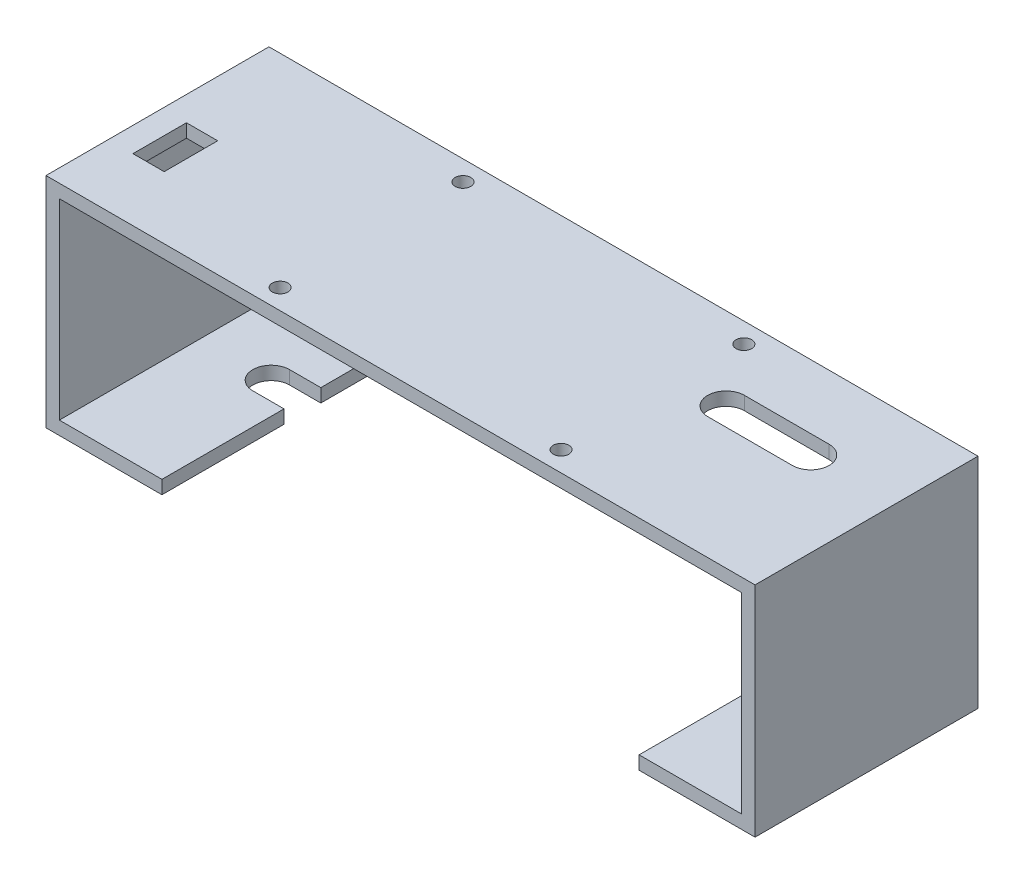
SolidWorks part; units mm, degrees
ref_plane "Front" through (0, 0, 0) normal (0, 0, 1) x (1, 0, 0)
ref_plane "Top" through (0, 0, 0) normal (0, 1, 0) x (1, 0, 0)
ref_plane "Right" through (0, 0, 0) normal (1, 0, 0) x (0, 0, -1)
sketch "Sketch1" plane through (0, 0, 0) normal (0, 1, 0) x (1, 0, 0)
  line L1 (-31.5, 20.5) -> (31.5, 20.5) construction
  line L2 (-31.5, 20.5) -> (-31.5, -20.5) construction
  line L3 (-31.5, -20.5) -> (31.5, -20.5) construction
  line L4 (31.5, 20.5) -> (31.5, -20.5) construction
  line L5 (-31.5, 20.5) -> (31.5, -20.5) construction
  line L6 (-31.5, -20.5) -> (31.5, 20.5) construction
  line L7 (-38.5, -18.5) -> (-24.5, -18.5) construction
  line L8 (-38.5, -18.5) -> (-38.5, 18.5) construction
  line L9 (-38.5, 18.5) -> (-24.5, 18.5) construction
  line L10 (-24.5, -18.5) -> (-24.5, 18.5) construction
  line L11 (-38.5, -18.5) -> (-24.5, 18.5) construction
  line L12 (-38.5, 18.5) -> (-24.5, -18.5) construction
  circle A0 centre (-31.5, 20.5) radius 1.75
  circle A1 centre (-31.5, -20.5) radius 1.75
  circle A2 centre (31.5, -20.5) radius 1.75
  circle A3 centre (31.5, 20.5) radius 1.75
  point P0 (0, 0)
  point P6 (-31.5, 0)
  dimension "D1" = 3.5
  dimension "D2" = 63
  dimension "D3" = 41
  dimension "D4" = 14
  dimension "D5" = 37
sketch "Sketch2" plane through (0, 0, 0) normal (0, 1, 0) x (1, 0, 0)
  line L1 (-52.5, 25) -> (52.5, 25)
  line L2 (-52.5, 25) -> (-52.5, -25) construction
  line L3 (-52.5, -25) -> (52.5, -25)
  line L4 (52.5, 25) -> (52.5, -25) construction
  line L5 (-52.5, 25) -> (52.5, -25) construction
  line L6 (-52.5, -25) -> (52.5, 25) construction
  line L7 (-52.5, 25) -> (-76.5, 25)
  line L8 (-76.5, 25) -> (-76.5, -25) construction
  line L9 (-76.5, -25) -> (-52.5, -25)
  line L10 (52.5, -25) -> (76.5, -25)
  line L11 (76.5, -25) -> (76.5, 25) construction
  line L12 (76.5, 25) -> (52.5, 25)
  line L13 (-76.5, -25) -> (-79.5, -25)
  line L14 (-79.5, -25) -> (-79.5, 25)
  line L15 (-79.5, 25) -> (-76.5, 25)
  line L16 (76.5, -25) -> (79.5, -25)
  line L17 (79.5, -25) -> (79.5, 25)
  line L18 (79.5, 25) -> (76.5, 25)
  dimension "D1" = 50
  dimension "D2" = 105
  dimension "D3" = 24
  dimension "D4" = 3
extrude "Boss-Extrude1" add sketch "Sketch2" along normal blind 3
sketch "Sketch4" plane through (0, 0, -25) normal (0, 0, -1) x (-1, 0, 0)
  line L0 (79.5, 0) -> (79.5, -46)
  line L1 (79.5, -46) -> (53.5, -46)
  line L2 (53.5, -46) -> (53.5, -43)
  line L3 (53.5, -43) -> (76.5, -43)
  line L4 (76.5, -43) -> (76.5, 0)
  line L5 (-79.5, 0) -> (79.5, 0) construction
  line L6 (76.5, 0) -> (79.5, 0)
  line L7 (52.5, 0) -> (76.5, 0) construction
  dimension "D1" = 43
  dimension "D2" = 23
extrude "Boss-Extrude2" add sketch "Sketch4" against normal up to surface (50 mm away) up to face at (0, 1.5, 25)
mirror "Mirror1" about plane through (0, 0, 0) normal (1, 0, 0) of "Boss-Extrude2"
sketch "Sketch5" plane through (0, -46, 0) normal (0, -1, 0) x (1, 0, 0)
  line L0 (-53.5, -2.375) -> (-60.5, -2.375)
  line L1 (-53.5, 25) -> (-53.5, -25) construction
  line L2 (-60.5, -10.625) -> (-53.5, -10.625)
  line L3 (-53.5, -10.625) -> (-53.5, -2.375)
  line L4 (-53.5, -25) -> (-79.5, -25) construction
  arc A0 (-60.5, -2.375) -> (-60.5, -10.625) centre (-60.5, -6.5) ccw
  dimension "D1" = 4.125
  dimension "D2" = 7
  dimension "D3" = 18.5
extrude "Cut-Extrude1" cut sketch "Sketch5" against normal up to next
sketch "Sketch6" plane through (0, 0, 0) normal (0, -1, 0) x (1, 0, 0)
  line L0 (41.5, -6.5) -> (60.5, -6.5) construction
  line L1 (41.5, -2.375) -> (60.5, -2.375)
  line L2 (41.5, -10.625) -> (60.5, -10.625)
  line L4 (53.5, 25) -> (53.5, -25) construction
  line L6 (76.5, -25) -> (-76.5, -25) construction
  arc A0 (41.5, -2.375) -> (41.5, -10.625) centre (41.5, -6.5) ccw
  arc A1 (60.5, -10.625) -> (60.5, -2.375) centre (60.5, -6.5) ccw
  arc A2 (-60.5, -2.375) -> (-60.5, -10.625) centre (-60.5, -6.5) ccw construction
  point P2 (51, -6.5)
  dimension "D2" = 7
  dimension "D3" = 12
  dimension "D1" = 18.5
extrude "Cut-Extrude2" cut sketch "Sketch6" against normal up to next
sketch "Sketch7" plane through (0, -46, 0) normal (0, -1, 0) x (1, 0, 0)
  line L2 (53.5, -25) -> (79.5, -25) construction
  line L3 (76.5, 25) -> (76.5, -25) construction
  line L7 (67, 11) -> (74, 11)
  line L8 (67, 11) -> (67, -1)
  line L9 (67, -1) -> (74, -1)
  line L10 (74, 11) -> (74, -1)
  line L11 (67, 11) -> (74, -1) construction
  line L12 (67, -1) -> (74, 11) construction
  point P5 (70.5, 5)
  dimension "D1" = 7
  dimension "D2" = 36
  dimension "D3" = 24
  dimension "D4" = 2.5
extrude "Cut-Extrude3" cut sketch "Sketch7" against normal up to next
sketch "Sketch8" plane through (0, 3, 0) normal (0, 1, 0) x (1, 0, 0)
  line L1 (-74, 1) -> (-67, 1)
  line L2 (-74, 1) -> (-74, -11)
  line L3 (-74, -11) -> (-67, -11)
  line L4 (-67, 1) -> (-67, -11)
  line L5 (-74, 1) -> (-67, -11) construction
  line L6 (-74, -11) -> (-67, 1) construction
  line L7 (67, -11) -> (67, 1) construction
  line L8 (67, 1) -> (74, 1) construction
  line L10 (-76.5, -25) -> (-76.5, 25) construction
  line L11 (79.5, 25) -> (-79.5, 25) construction
  point P0 (-70.5, -5)
  dimension "D1" = 2.5
  dimension "D2" = 24
extrude "Cut-Extrude5" cut sketch "Sketch8" against normal up to next
extrude "Cut-Extrude7" cut sketch "Sketch1" along normal up to next contours A0 | A1 | A2 | A3
